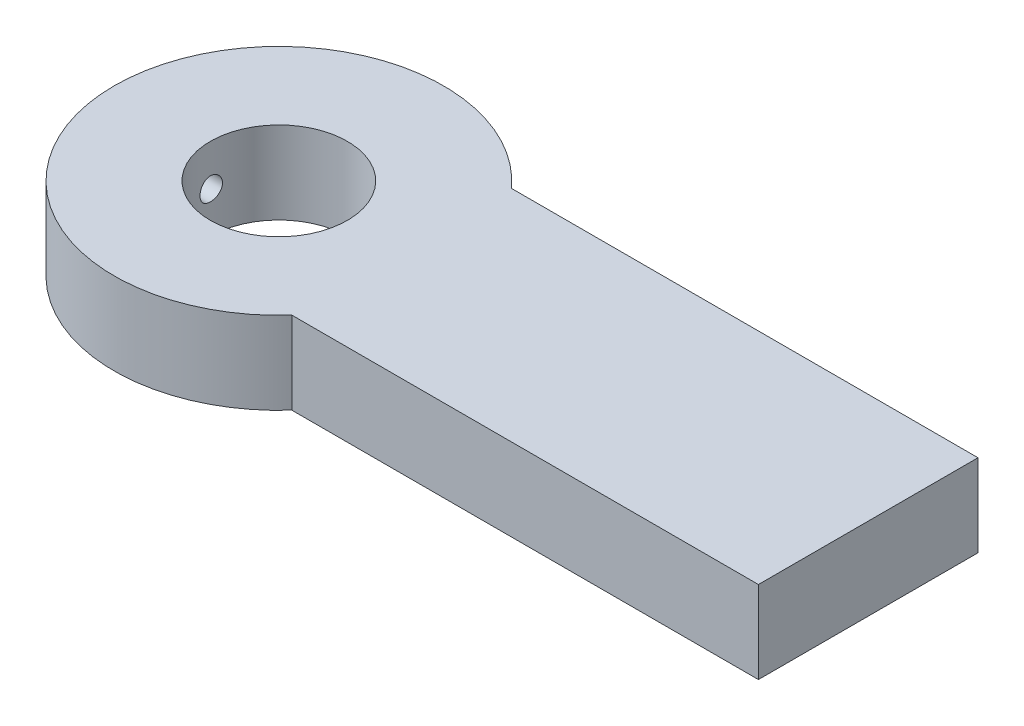
SolidWorks part; units mm, degrees
ref_plane "Front" through (0, 0, 0) normal (0, 0, 1) x (1, 0, 0)
ref_plane "Top" through (0, 0, 0) normal (0, 1, 0) x (1, 0, 0)
ref_plane "Right" through (0, 0, 0) normal (1, 0, 0) x (0, 0, -1)
sketch "Sketch1" plane through (0, 0, 0) normal (0, 1, 0) x (1, 0, 0)
  line L0 (22.3607, 20) -> (107.3607, 20)
  line L1 (107.3607, 20) -> (107.3607, -20)
  line L2 (107.3607, -20) -> (22.3607, -20)
  circle A0 centre (0, 0) radius 12.48
  arc A1 (22.3607, 20) -> (22.3607, -20) centre (0, 0) ccw
  point P3 (0, 0)
  point P6 (107.3607, 0)
  point P9 (0, 0)
  point P10 (0, 0)
  dimension "D1" = 24.96
  dimension "D4" = 30
  dimension "D2" = 40
  dimension "D3" = 85
extrude "Boss-Extrude1" add sketch "Sketch1" along normal blind 15
sketch "Sketch2" plane through (0, 0, 0) normal (1, 0, 0) x (0, 0, -1)
  circle A1 centre (0, 7.5) radius 2.05
  point P3 (0, 0)
  dimension "D1" = 7.5
  dimension "D2" = 4.1
extrude "Cut-Extrude1" cut sketch "Sketch2" against normal through all
